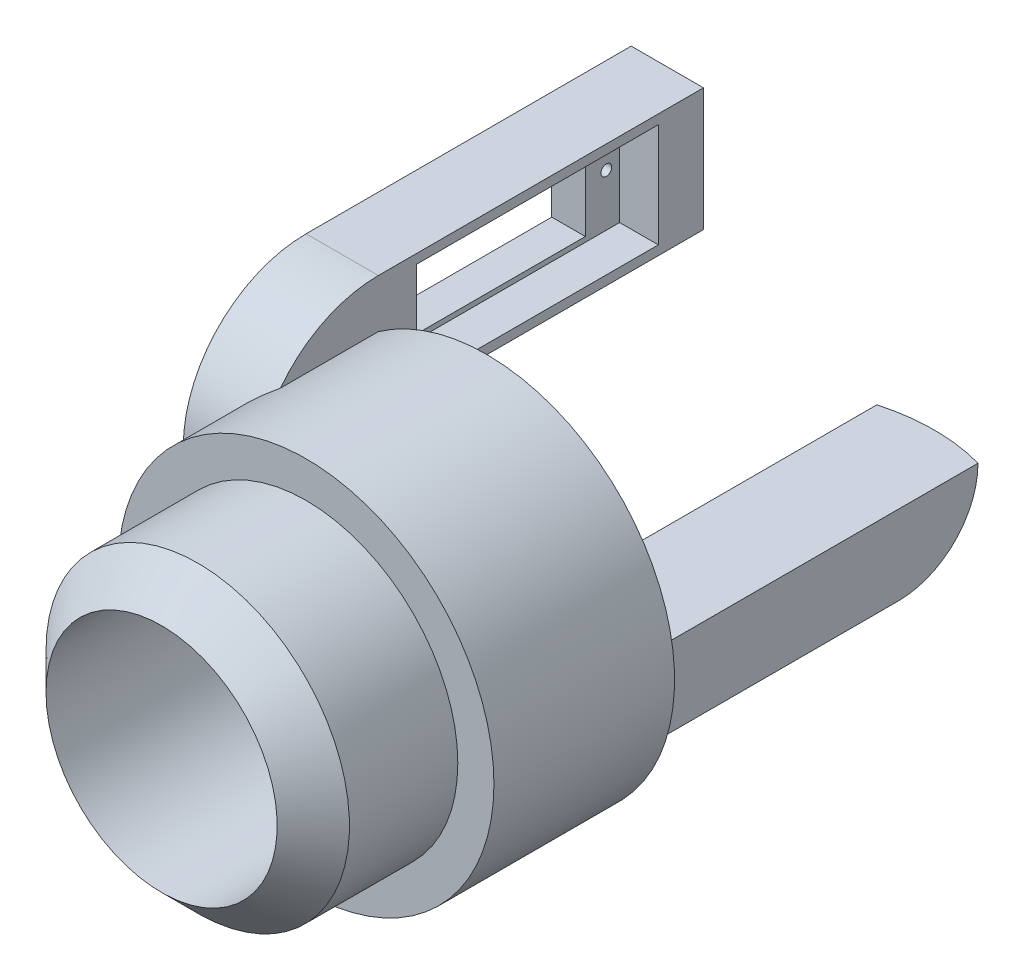
SolidWorks part; units mm, degrees
ref_plane "Front Plane" through (0, 0, 0) normal (0, 0, 1) x (1, 0, 0)
ref_plane "Top Plane" through (0, 0, 0) normal (0, 1, 0) x (1, 0, 0)
ref_plane "Right Plane" through (0, 0, 0) normal (1, 0, 0) x (0, 0, -1)
sketch "Sketch15" plane through (0, 0, 0) normal (0, 0, 1) x (1, 0, 0)
  circle A2 centre (0, 0) radius 26
  circle A3 centre (0, 0) radius 21
  dimension "D1" = 52
  dimension "D2" = 5
extrude "Boss-Extrude2" add sketch "Sketch15" along normal blind 20
sketch "Sketch18" plane through (0, 0, 20) normal (0, 0, 1) x (1, 0, 0)
  circle A1 centre (0, 0) radius 21 construction
  circle A3 centre (0, 0) radius 21
  circle A4 centre (0, 0) radius 16
  dimension "D1" = 5
extrude "Boss-Extrude5" add sketch "Sketch18" along normal blind 30 from offset 10 offset against normal yes
chamfer "Chamfer1" distance 5 angle 45 1 edges at (21, 0, 40)
sketch "Sketch21" plane through (0, 0, 0) normal (0, 0, -1) x (-1, 0, 0)
  circle A0 centre (0, 0) radius 10
  circle A1 centre (0, 0) radius 26
  circle A2 centre (0, 0) radius 26
  dimension "D2" = 20
  dimension "D1" = 0
extrude "Boss-Extrude6" add sketch "Sketch21" along normal blind 5
sketch "Sketch23" plane through (0, 0, -5) normal (0, 0, -1) x (-1, 0, 0)
  line L0 (-7, -25.04) -> (-7, -14.04)
  line L1 (0, 0) -> (0, -32.0565) construction
  line L2 (-7, -14.04) -> (7, -14.04)
  line L3 (7, -25.04) -> (7, -14.04)
  circle A0 centre (0, 0) radius 26 construction
  arc A1 (-7, -25.04) -> (7, -25.04) centre (0, 0) ccw
  point P10 (0, -14.04)
  dimension "D1" = 14
  dimension "D2" = 11
extrude "Boss-Extrude8" add sketch "Sketch23" along normal blind 50
sketch "Sketch25" plane through (0, 0, -55) normal (0, 0, -1) x (-1, 0, 0)
  line L0 (-7, -14.04) -> (-7, -25.04) construction
  line L1 (-7, -14.04) -> (-7, -25.04)
  line L2 (7, -14.04) -> (-7, -14.04) construction
  line L3 (7, -25.04) -> (7, -14.04) construction
  line L4 (7, -14.04) -> (-7, -14.04)
  line L5 (7, -25.04) -> (7, -14.04)
  arc A0 (-7, -25.04) -> (7, -25.04) centre (0, 0) ccw construction
  arc A1 (-7, -25.04) -> (7, -25.04) centre (0, 0) ccw
revolve "Revolve2" add sketch "Sketch25" angle 90 about L4
sketch "Sketch26" plane through (0, 0, 0) normal (1, 0, 0) x (0, 0, -1)
  line L0 (5, -25.04) -> (5, 26) construction
  line L1 (5, 27.96) -> (50, 27.96)
  line L2 (5, 27.96) -> (5, 10.96)
  line L3 (5, 10.96) -> (50, 10.96)
  line L4 (50, 27.96) -> (50, 10.96)
  line L6 (66, -14.04) -> (5, -14.04) construction
  dimension "D1" = 17
  dimension "D2" = 45
  dimension "D3" = 25
extrude "Boss-Extrude9" add sketch "Sketch26" along normal mid plane 10 from offset 20 offset against normal yes
sketch "Sketch27" plane through (-15, 0, 0) normal (1, 0, 0) x (0, 0, -1)
  line L0 (5, 27.96) -> (5, 21.2368) construction
  line L1 (50, 27.96) -> (5, 27.96) construction
  line L2 (5, 10.96) -> (50, 10.96) construction
  line L6 (15, 25.96) -> (15, 12.96)
  line L13 (15, 12.96) -> (39, 12.96)
  line L14 (39, 12.96) -> (39, 25.96)
  line L15 (39, 25.96) -> (15, 25.96)
  dimension "D1" = 24
  dimension "D2" = 2
  dimension "D3" = 2
  dimension "D4" = 10
extrude "Cut-Extrude1" cut sketch "Sketch27" against normal up to next
sketch "Sketch28" plane through (0, 0, -5) normal (0, 0, 1) x (1, 0, 0)
  line L4 (-25, 10.96) -> (-23.5771, 10.96)
  line L5 (-15, 21.2368) -> (-15, 27.96)
  line L6 (-15, 27.96) -> (-25, 27.96)
  line L7 (-25, 27.96) -> (-25, 10.96)
  line L8 (-25, 10.96) -> (-23.5771, 10.96)
  line L9 (-15, 21.2368) -> (-15, 27.96)
  line L10 (-15, 27.96) -> (-25, 27.96)
  line L11 (-25, 27.96) -> (-25, 10.96)
  arc A1 (-15, 21.2368) -> (-23.5771, 10.96) centre (0, 0) ccw
  arc A2 (-15, 21.2368) -> (-23.5771, 10.96) centre (0, 0) ccw
  dimension "D1" = 0
revolve "Revolve3" add sketch "Sketch28" angle 90 about L8
sketch "Sketch29" plane through (0, 10.96, 0) normal (0, -1, 0) x (1, 0, 0)
  line L1 (-23.5771, -5) -> (-25, -5)
  line L2 (-25, 12) -> (-25, -50) construction
  line L3 (-25, -5) -> (-25, 12)
  line L4 (-25, 12) -> (-23.5771, 12)
  line L5 (-23.5771, 12) -> (-23.5771, -5)
revolve "Revolve4" add sketch "Sketch29" angle 90 about L5 reverse direction yes
sketch "Sketch31" plane through (-15, 0, 0) normal (1, 0, 0) x (0, 0, -1)
  line L0 (39, 19.46) -> (41.9, 19.46) construction
  line L1 (39, 12.96) -> (39, 25.96) construction
  line L3 (15, 19.46) -> (11.6, 19.46) construction
  line L4 (15, 25.96) -> (15, 12.96) construction
  circle A0 centre (41.9, 19.46) radius 0.75
  circle A1 centre (11.6, 19.46) radius 0.75
  dimension "D2" = 1.5
  dimension "D1" = 2.9
  dimension "D3" = 3.4
extrude "Cut-Extrude2" cut sketch "Sketch31" against normal through all
sketch "Sketch32" plane through (-15, 0, 0) normal (1, 0, 0) x (0, 0, -1)
  line L0 (15, 25.96) -> (39, 12.96) construction
  line L1 (15, 12.96) -> (39, 25.96) construction
  line L3 (10.25, 12.26) -> (43.75, 12.26)
  line L4 (10.25, 12.26) -> (10.25, 26.66)
  line L5 (10.25, 26.66) -> (43.75, 26.66)
  line L6 (43.75, 12.26) -> (43.75, 26.66)
  line L7 (10.25, 12.26) -> (43.75, 26.66) construction
  line L8 (10.25, 26.66) -> (43.75, 12.26) construction
  point P8 (27, 19.46)
  point P9 (27, 19.46)
  dimension "D1" = 33.5
  dimension "D2" = 14.4
extrude "Cut-Extrude3" cut sketch "Sketch32" against normal blind 5.35
